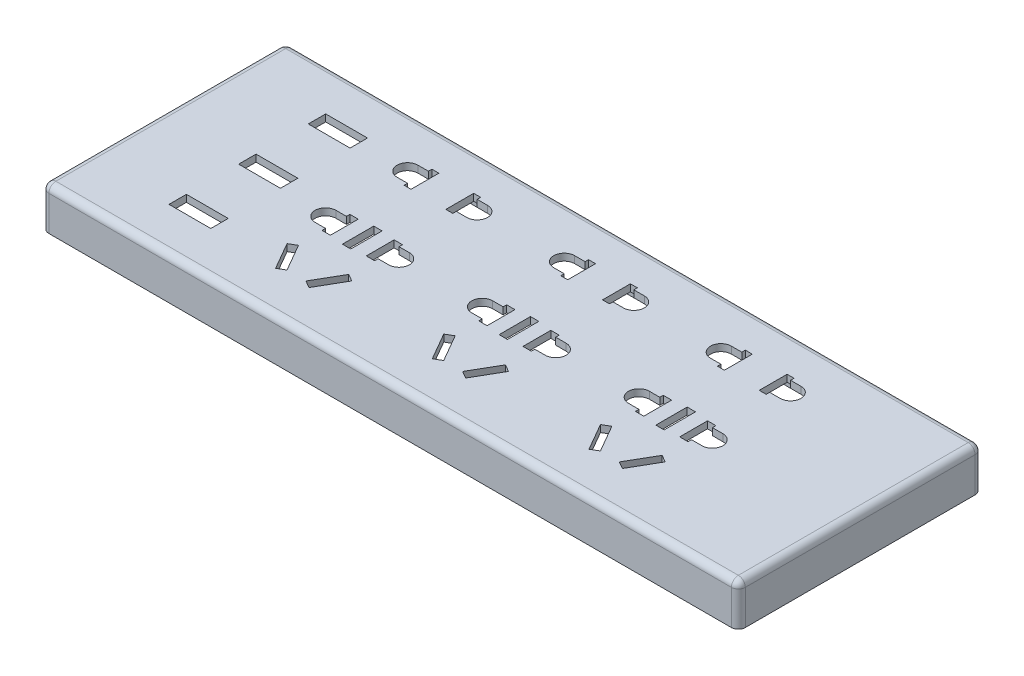
SolidWorks part; units mm, degrees
material "ABS"
ref_plane "前视基准面" through (0, 0, 0) normal (0, 0, 1) x (1, 0, 0)
ref_plane "上视基准面" through (0, 0, 0) normal (0, 1, 0) x (1, 0, 0)
ref_plane "右视基准面" through (0, 0, 0) normal (1, 0, 0) x (0, 0, -1)
ref_plane "BoxInnerTop" through (0, 0, 0) normal (0, 1, 0) x (1, 0, 0)
ref_plane "ConnectFace" through (0, -10, 0) normal (0, 1, 0) x (1, 0, 0)
sketch "SketchRec" plane through (0, 0, 0) normal (0, 1, 0) x (1, 0, 0)
  line L1 (-100, -35) -> (100, -35)
  line L2 (-100, -35) -> (-100, 35)
  line L3 (-100, 35) -> (100, 35)
  line L4 (100, -35) -> (100, 35)
  line L5 (-100, -35) -> (100, 35) construction
  line L6 (-100, 35) -> (100, -35) construction
  point P0 (0, 0)
  dimension "L" = 200
  dimension "KD" = 70
extrude "RectangleBox" add sketch "SketchRec" along normal blind 2 and the other way blind 10
fillet "RectangleR" radius 2 8 edges at (-100, -4, 35) (-100, -4, -35) (100, -4, -35) (100, -4, 35) (100, 2, 0) (0, 2, -35) (-100, 2, 0) (0, 2, 35)
shell "RectangleC" thickness 2 removed face at (0, -10, 0)
sketch "SketchCircle" [suppressed] plane through (0, 0, 0) normal (0, 1, 0) x (1, 0, 0)
  circle A0 centre (0, 0) radius 80
  dimension "D1" = 160
extrude "CircleBox" [suppressed] add sketch "SketchCircle" along normal blind 2 and the other way blind 10 contours A0
fillet "CircleR" [suppressed] radius 2
shell "CircleC" [suppressed] thickness 2
sketch "SLEDCut" plane through (0, -10, 0) normal (0, 1, 0) x (1, 0, 0)
  line L4 (-91.5, -5) -> (-88.5, -5)
  line L5 (-88.5, -5) -> (-88.5, 5)
  line L6 (-88.5, 5) -> (-91.5, 5)
  line L7 (-91.5, 5) -> (-91.5, -5)
  line L8 (-91.5, -5) -> (-88.5, -5)
  line L9 (-88.5, -5) -> (-88.5, 5)
  line L10 (-88.5, 5) -> (-91.5, 5)
  line L11 (-91.5, 5) -> (-91.5, -5)
  dimension "D1" = 0
extrude "FLEDCut" [suppressed] cut sketch "SLEDCut" along normal through all
sketch "SSlotA" plane through (0, -10, 0) normal (0, 1, 0) x (1, 0, 0)
  line L4 (-38.8, 1.5) -> (-41.2, 1.5)
  line L5 (-38.8, -7.5) -> (-38.8, 1.5)
  line L6 (-41.2, -7.5) -> (-38.8, -7.5)
  line L7 (-45.15, -7) -> (-45.15, 1)
  line L8 (-47.55, -7) -> (-45.15, -7)
  line L9 (-47.55, -6) -> (-47.55, -7)
  line L10 (-50.55, -6) -> (-47.55, -6)
  line L11 (-47.55, 0) -> (-50.55, 0)
  line L12 (-47.55, 1) -> (-47.55, 0)
  line L13 (-45.15, 1) -> (-47.55, 1)
  line L14 (-45.15, -7) -> (-45.15, 1)
  line L15 (-47.55, -7) -> (-45.15, -7)
  line L16 (-47.55, -6) -> (-47.55, -7)
  line L17 (-50.55, -6) -> (-47.55, -6)
  line L18 (-47.55, 0) -> (-50.55, 0)
  line L19 (-47.55, 1) -> (-47.55, 0)
  line L20 (-45.15, 1) -> (-47.55, 1)
  line L21 (-41.2, 1.5) -> (-41.2, -7.5)
  line L22 (-38.8, 1.5) -> (-41.2, 1.5)
  line L23 (-38.8, -7.5) -> (-38.8, 1.5)
  line L24 (-41.2, -7.5) -> (-38.8, -7.5)
  line L25 (-41.2, 1.5) -> (-41.2, -7.5)
  line L26 (-37.2831, -21.8942) -> (-35.2047, -23.0942)
  line L27 (-35.2047, -23.0942) -> (-30.7047, -15.3)
  line L28 (-30.7047, -15.3) -> (-32.7831, -14.1)
  line L29 (-32.45, 0) -> (-32.45, 1)
  line L30 (-29.45, 0) -> (-32.45, 0)
  line L31 (-32.45, -6) -> (-29.45, -6)
  line L32 (-32.45, -7) -> (-32.45, -6)
  line L33 (-34.85, -7) -> (-32.45, -7)
  line L34 (-34.85, 1) -> (-34.85, -7)
  line L35 (-32.45, 1) -> (-34.85, 1)
  line L36 (-32.45, 0) -> (-32.45, 1)
  line L37 (-29.45, 0) -> (-32.45, 0)
  line L38 (-32.45, -6) -> (-29.45, -6)
  line L39 (-32.45, -7) -> (-32.45, -6)
  line L40 (-34.85, -7) -> (-32.45, -7)
  line L41 (-34.85, 1) -> (-34.85, -7)
  line L42 (-32.45, 1) -> (-34.85, 1)
  line L43 (-32.7831, -14.1) -> (-37.2831, -21.8942)
  line L44 (-37.2831, -21.8942) -> (-35.2047, -23.0942)
  line L45 (-35.2047, -23.0942) -> (-30.7047, -15.3)
  line L46 (-30.7047, -15.3) -> (-32.7831, -14.1)
  line L47 (-32.7831, -14.1) -> (-37.2831, -21.8942)
  line L48 (-49.2953, -15.3) -> (-44.7953, -23.0942)
  line L49 (-47.2169, -14.1) -> (-49.2953, -15.3)
  line L50 (-42.7169, -21.8942) -> (-47.2169, -14.1)
  line L51 (-44.7953, -23.0942) -> (-42.7169, -21.8942)
  line L52 (-49.2953, -15.3) -> (-44.7953, -23.0942)
  line L53 (-47.2169, -14.1) -> (-49.2953, -15.3)
  line L54 (-42.7169, -21.8942) -> (-47.2169, -14.1)
  line L55 (-44.7953, -23.0942) -> (-42.7169, -21.8942)
  arc A1 (-50.55, 0) -> (-50.55, -6) centre (-50.55, -3) ccw
  arc A2 (-50.55, 0) -> (-50.55, -6) centre (-50.55, -3) ccw
  arc A3 (-29.45, -6) -> (-29.45, 0) centre (-29.45, -3) ccw
  arc A4 (-29.45, -6) -> (-29.45, 0) centre (-29.45, -3) ccw
  dimension "D1" = 0
  dimension "D2" = 0
  dimension "D3" = 0
  dimension "D4" = 0
  dimension "D5" = 0
extrude "FSlotACut" cut sketch "SSlotA" along normal through all
sketch "SSlotA2" plane through (0, -10, 0) normal (0, 1, 0) x (1, 0, 0)
  line L4 (6.2, 1.5) -> (3.8, 1.5)
  line L5 (6.2, -7.5) -> (6.2, 1.5)
  line L6 (3.8, -7.5) -> (6.2, -7.5)
  line L7 (-0.15, -7) -> (-0.15, 1)
  line L8 (-2.55, -7) -> (-0.15, -7)
  line L9 (-2.55, -6) -> (-2.55, -7)
  line L10 (-5.55, -6) -> (-2.55, -6)
  line L11 (-2.55, 0) -> (-5.55, 0)
  line L12 (-2.55, 1) -> (-2.55, 0)
  line L13 (-0.15, 1) -> (-2.55, 1)
  line L14 (-0.15, -7) -> (-0.15, 1)
  line L15 (-2.55, -7) -> (-0.15, -7)
  line L16 (-2.55, -6) -> (-2.55, -7)
  line L17 (-5.55, -6) -> (-2.55, -6)
  line L18 (-2.55, 0) -> (-5.55, 0)
  line L19 (-2.55, 1) -> (-2.55, 0)
  line L20 (-0.15, 1) -> (-2.55, 1)
  line L21 (3.8, 1.5) -> (3.8, -7.5)
  line L22 (6.2, 1.5) -> (3.8, 1.5)
  line L23 (6.2, -7.5) -> (6.2, 1.5)
  line L24 (3.8, -7.5) -> (6.2, -7.5)
  line L25 (3.8, 1.5) -> (3.8, -7.5)
  line L26 (7.7169, -21.8942) -> (9.7953, -23.0942)
  line L27 (9.7953, -23.0942) -> (14.2953, -15.3)
  line L28 (14.2953, -15.3) -> (12.2169, -14.1)
  line L29 (12.55, 0) -> (12.55, 1)
  line L30 (15.55, 0) -> (12.55, 0)
  line L31 (12.55, -6) -> (15.55, -6)
  line L32 (12.55, -7) -> (12.55, -6)
  line L33 (10.15, -7) -> (12.55, -7)
  line L34 (10.15, 1) -> (10.15, -7)
  line L35 (12.55, 1) -> (10.15, 1)
  line L36 (12.55, 0) -> (12.55, 1)
  line L37 (15.55, 0) -> (12.55, 0)
  line L38 (12.55, -6) -> (15.55, -6)
  line L39 (12.55, -7) -> (12.55, -6)
  line L40 (10.15, -7) -> (12.55, -7)
  line L41 (10.15, 1) -> (10.15, -7)
  line L42 (12.55, 1) -> (10.15, 1)
  line L43 (12.2169, -14.1) -> (7.7169, -21.8942)
  line L44 (7.7169, -21.8942) -> (9.7953, -23.0942)
  line L45 (9.7953, -23.0942) -> (14.2953, -15.3)
  line L46 (14.2953, -15.3) -> (12.2169, -14.1)
  line L47 (12.2169, -14.1) -> (7.7169, -21.8942)
  line L48 (-4.2953, -15.3) -> (0.2047, -23.0942)
  line L49 (-2.2169, -14.1) -> (-4.2953, -15.3)
  line L50 (2.2831, -21.8942) -> (-2.2169, -14.1)
  line L51 (0.2047, -23.0942) -> (2.2831, -21.8942)
  line L52 (-4.2953, -15.3) -> (0.2047, -23.0942)
  line L53 (-2.2169, -14.1) -> (-4.2953, -15.3)
  line L54 (2.2831, -21.8942) -> (-2.2169, -14.1)
  line L55 (0.2047, -23.0942) -> (2.2831, -21.8942)
  arc A1 (-5.55, 0) -> (-5.55, -6) centre (-5.55, -3) ccw
  arc A2 (-5.55, 0) -> (-5.55, -6) centre (-5.55, -3) ccw
  arc A3 (15.55, -6) -> (15.55, 0) centre (15.55, -3) ccw
  arc A4 (15.55, -6) -> (15.55, 0) centre (15.55, -3) ccw
  dimension "D1" = 0
  dimension "D2" = 0
  dimension "D3" = 0
  dimension "D4" = 0
  dimension "D5" = 0
extrude "FSlotA2Cut" cut sketch "SSlotA2" along normal through all
sketch "SSlotA3" plane through (0, -10, 0) normal (0, 1, 0) x (1, 0, 0)
  line L4 (51.2, 1.5) -> (48.8, 1.5)
  line L5 (51.2, -7.5) -> (51.2, 1.5)
  line L6 (48.8, -7.5) -> (51.2, -7.5)
  line L7 (44.85, -7) -> (44.85, 1)
  line L8 (42.45, -7) -> (44.85, -7)
  line L9 (42.45, -6) -> (42.45, -7)
  line L10 (39.45, -6) -> (42.45, -6)
  line L11 (42.45, 0) -> (39.45, 0)
  line L12 (42.45, 1) -> (42.45, 0)
  line L13 (44.85, 1) -> (42.45, 1)
  line L14 (44.85, -7) -> (44.85, 1)
  line L15 (42.45, -7) -> (44.85, -7)
  line L16 (42.45, -6) -> (42.45, -7)
  line L17 (39.45, -6) -> (42.45, -6)
  line L18 (42.45, 0) -> (39.45, 0)
  line L19 (42.45, 1) -> (42.45, 0)
  line L20 (44.85, 1) -> (42.45, 1)
  line L21 (48.8, 1.5) -> (48.8, -7.5)
  line L22 (51.2, 1.5) -> (48.8, 1.5)
  line L23 (51.2, -7.5) -> (51.2, 1.5)
  line L24 (48.8, -7.5) -> (51.2, -7.5)
  line L25 (48.8, 1.5) -> (48.8, -7.5)
  line L26 (52.7169, -21.8942) -> (54.7953, -23.0942)
  line L27 (54.7953, -23.0942) -> (59.2953, -15.3)
  line L28 (59.2953, -15.3) -> (57.2169, -14.1)
  line L29 (57.55, 0) -> (57.55, 1)
  line L30 (60.55, 0) -> (57.55, 0)
  line L31 (57.55, -6) -> (60.55, -6)
  line L32 (57.55, -7) -> (57.55, -6)
  line L33 (55.15, -7) -> (57.55, -7)
  line L34 (55.15, 1) -> (55.15, -7)
  line L35 (57.55, 1) -> (55.15, 1)
  line L36 (57.55, 0) -> (57.55, 1)
  line L37 (60.55, 0) -> (57.55, 0)
  line L38 (57.55, -6) -> (60.55, -6)
  line L39 (57.55, -7) -> (57.55, -6)
  line L40 (55.15, -7) -> (57.55, -7)
  line L41 (55.15, 1) -> (55.15, -7)
  line L42 (57.55, 1) -> (55.15, 1)
  line L43 (57.2169, -14.1) -> (52.7169, -21.8942)
  line L44 (52.7169, -21.8942) -> (54.7953, -23.0942)
  line L45 (54.7953, -23.0942) -> (59.2953, -15.3)
  line L46 (59.2953, -15.3) -> (57.2169, -14.1)
  line L47 (57.2169, -14.1) -> (52.7169, -21.8942)
  line L48 (40.7047, -15.3) -> (45.2047, -23.0942)
  line L49 (42.7831, -14.1) -> (40.7047, -15.3)
  line L50 (47.2831, -21.8942) -> (42.7831, -14.1)
  line L51 (45.2047, -23.0942) -> (47.2831, -21.8942)
  line L52 (40.7047, -15.3) -> (45.2047, -23.0942)
  line L53 (42.7831, -14.1) -> (40.7047, -15.3)
  line L54 (47.2831, -21.8942) -> (42.7831, -14.1)
  line L55 (45.2047, -23.0942) -> (47.2831, -21.8942)
  arc A1 (39.45, 0) -> (39.45, -6) centre (39.45, -3) ccw
  arc A2 (39.45, 0) -> (39.45, -6) centre (39.45, -3) ccw
  arc A3 (60.55, -6) -> (60.55, 0) centre (60.55, -3) ccw
  arc A4 (60.55, -6) -> (60.55, 0) centre (60.55, -3) ccw
  dimension "D1" = 0
  dimension "D2" = 0
  dimension "D3" = 0
  dimension "D4" = 0
  dimension "D5" = 0
extrude "FSlotA3Cut" cut sketch "SSlotA3" along normal through all
sketch "SSlotB" plane through (0, -10, 0) normal (0, 1, 0) x (1, 0, 0)
  line L7 (-45, 16) -> (-45, 24)
  line L8 (-47, 16) -> (-45, 16)
  line L9 (-47, 17) -> (-47, 16)
  line L10 (-50, 17) -> (-47, 17)
  line L11 (-47, 23) -> (-50, 23)
  line L12 (-47, 24) -> (-47, 23)
  line L13 (-45, 24) -> (-47, 24)
  line L14 (-45, 16) -> (-45, 24)
  line L15 (-47, 16) -> (-45, 16)
  line L16 (-47, 17) -> (-47, 16)
  line L17 (-50, 17) -> (-47, 17)
  line L18 (-47, 23) -> (-50, 23)
  line L19 (-47, 24) -> (-47, 23)
  line L20 (-45, 24) -> (-47, 24)
  line L21 (-33, 17) -> (-30, 17)
  line L22 (-30, 23) -> (-33, 23)
  line L23 (-33, 23) -> (-33, 24)
  line L24 (-33, 24) -> (-35, 24)
  line L25 (-35, 24) -> (-35, 16)
  line L26 (-35, 16) -> (-33, 16)
  line L27 (-33, 16) -> (-33, 17)
  line L28 (-33, 17) -> (-30, 17)
  line L29 (-30, 23) -> (-33, 23)
  line L30 (-33, 23) -> (-33, 24)
  line L31 (-33, 24) -> (-35, 24)
  line L32 (-35, 24) -> (-35, 16)
  line L33 (-35, 16) -> (-33, 16)
  line L34 (-33, 16) -> (-33, 17)
  arc A1 (-50, 23) -> (-50, 17) centre (-50, 20) ccw
  arc A2 (-50, 23) -> (-50, 17) centre (-50, 20) ccw
  arc A3 (-30, 17) -> (-30, 23) centre (-30, 20) ccw
  arc A4 (-30, 17) -> (-30, 23) centre (-30, 20) ccw
  dimension "D1" = 0
  dimension "D2" = 0
extrude "FSlotBCut" cut sketch "SSlotB" along normal through all
sketch "SSlotB2" plane through (0, -10, 0) normal (0, 1, 0) x (1, 0, 0)
  line L7 (0, 16) -> (0, 24)
  line L8 (-2, 16) -> (0, 16)
  line L9 (-2, 17) -> (-2, 16)
  line L10 (-5, 17) -> (-2, 17)
  line L11 (-2, 23) -> (-5, 23)
  line L12 (-2, 24) -> (-2, 23)
  line L13 (0, 24) -> (-2, 24)
  line L14 (0, 16) -> (0, 24)
  line L15 (-2, 16) -> (0, 16)
  line L16 (-2, 17) -> (-2, 16)
  line L17 (-5, 17) -> (-2, 17)
  line L18 (-2, 23) -> (-5, 23)
  line L19 (-2, 24) -> (-2, 23)
  line L20 (0, 24) -> (-2, 24)
  line L21 (12, 17) -> (15, 17)
  line L22 (15, 23) -> (12, 23)
  line L23 (12, 23) -> (12, 24)
  line L24 (12, 24) -> (10, 24)
  line L25 (10, 24) -> (10, 16)
  line L26 (10, 16) -> (12, 16)
  line L27 (12, 16) -> (12, 17)
  line L28 (12, 17) -> (15, 17)
  line L29 (15, 23) -> (12, 23)
  line L30 (12, 23) -> (12, 24)
  line L31 (12, 24) -> (10, 24)
  line L32 (10, 24) -> (10, 16)
  line L33 (10, 16) -> (12, 16)
  line L34 (12, 16) -> (12, 17)
  arc A1 (-5, 23) -> (-5, 17) centre (-5, 20) ccw
  arc A2 (-5, 23) -> (-5, 17) centre (-5, 20) ccw
  arc A3 (15, 17) -> (15, 23) centre (15, 20) ccw
  arc A4 (15, 17) -> (15, 23) centre (15, 20) ccw
  dimension "D1" = 0
  dimension "D2" = 0
extrude "FSlotB2Cut" cut sketch "SSlotB2" along normal through all
sketch "SSlotB3" plane through (0, -10, 0) normal (0, 1, 0) x (1, 0, 0)
  line L7 (45, 16) -> (45, 24)
  line L8 (43, 16) -> (45, 16)
  line L9 (43, 17) -> (43, 16)
  line L10 (40, 17) -> (43, 17)
  line L11 (43, 23) -> (40, 23)
  line L12 (43, 24) -> (43, 23)
  line L13 (45, 24) -> (43, 24)
  line L14 (45, 16) -> (45, 24)
  line L15 (43, 16) -> (45, 16)
  line L16 (43, 17) -> (43, 16)
  line L17 (40, 17) -> (43, 17)
  line L18 (43, 23) -> (40, 23)
  line L19 (43, 24) -> (43, 23)
  line L20 (45, 24) -> (43, 24)
  line L21 (57, 17) -> (60, 17)
  line L22 (60, 23) -> (57, 23)
  line L23 (57, 23) -> (57, 24)
  line L24 (57, 24) -> (55, 24)
  line L25 (55, 24) -> (55, 16)
  line L26 (55, 16) -> (57, 16)
  line L27 (57, 16) -> (57, 17)
  line L28 (57, 17) -> (60, 17)
  line L29 (60, 23) -> (57, 23)
  line L30 (57, 23) -> (57, 24)
  line L31 (57, 24) -> (55, 24)
  line L32 (55, 24) -> (55, 16)
  line L33 (55, 16) -> (57, 16)
  line L34 (57, 16) -> (57, 17)
  arc A1 (40, 23) -> (40, 17) centre (40, 20) ccw
  arc A2 (40, 23) -> (40, 17) centre (40, 20) ccw
  arc A3 (60, 17) -> (60, 23) centre (60, 20) ccw
  arc A4 (60, 17) -> (60, 23) centre (60, 20) ccw
  dimension "D1" = 0
  dimension "D2" = 0
extrude "FSlotB3Cut" cut sketch "SSlotB3" along normal through all
sketch "SSlotC" plane through (0, -10, 0) normal (0, 1, 0) x (1, 0, 0)
  line L4 (-64, 17.5) -> (-64, 22.5)
  line L5 (-64, 22.5) -> (-76, 22.5)
  line L6 (-76, 22.5) -> (-76, 17.5)
  line L7 (-76, 17.5) -> (-64, 17.5)
  line L8 (-64, 17.5) -> (-64, 22.5)
  line L9 (-64, 22.5) -> (-76, 22.5)
  line L10 (-76, 22.5) -> (-76, 17.5)
  line L11 (-76, 17.5) -> (-64, 17.5)
  dimension "D1" = 0
extrude "FSlotCCut" cut sketch "SSlotC" along normal through all
sketch "SSlotC2" plane through (0, -10, 0) normal (0, 1, 0) x (1, 0, 0)
  line L4 (-64, -2.5) -> (-64, 2.5)
  line L5 (-64, 2.5) -> (-76, 2.5)
  line L6 (-76, 2.5) -> (-76, -2.5)
  line L7 (-76, -2.5) -> (-64, -2.5)
  line L8 (-64, -2.5) -> (-64, 2.5)
  line L9 (-64, 2.5) -> (-76, 2.5)
  line L10 (-76, 2.5) -> (-76, -2.5)
  line L11 (-76, -2.5) -> (-64, -2.5)
  dimension "D1" = 0
extrude "FSlotC2Cut" cut sketch "SSlotC2" along normal through all
sketch "SSlotC3" plane through (0, -10, 0) normal (0, 1, 0) x (1, 0, 0)
  line L4 (-64, -22.5) -> (-64, -17.5)
  line L5 (-64, -17.5) -> (-76, -17.5)
  line L6 (-76, -17.5) -> (-76, -22.5)
  line L7 (-76, -22.5) -> (-64, -22.5)
  line L8 (-64, -22.5) -> (-64, -17.5)
  line L9 (-64, -17.5) -> (-76, -17.5)
  line L10 (-76, -17.5) -> (-76, -22.5)
  line L11 (-76, -22.5) -> (-64, -22.5)
  dimension "D1" = 0
extrude "FSlotC3Cut" cut sketch "SSlotC3" along normal through all
equation "\"H\"= 10"
equation "\"Tn\"= 2"
equation "\"D1@RectangleBox\"=\"Tn\""
equation "\"D2@RectangleBox\"=\"H\""
equation "\"D1@CircleBox\"=\"Tn\""
equation "\"D2@CircleBox\"=\"H\""
equation "\"DisCt@ConnectFace\"=\"H\""
